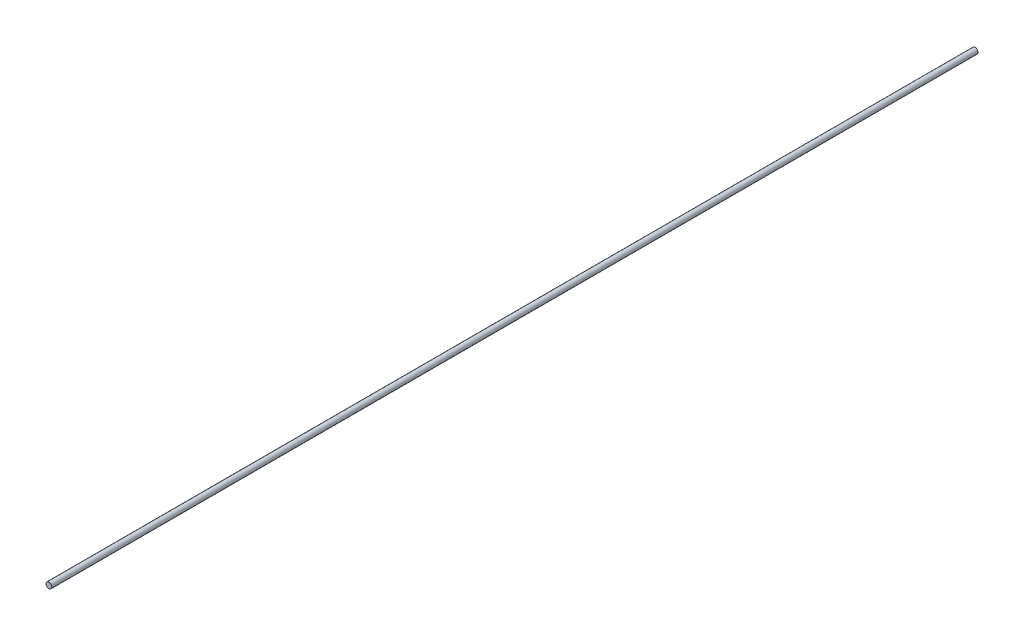
SolidWorks part; units mm, degrees
material "Hexcel AS4C (3000 Filaments)"
ref_plane "Front Plane" through (0, 0, 0) normal (0, 0, 1) x (1, 0, 0)
ref_plane "Top Plane" through (0, 0, 0) normal (0, 1, 0) x (1, 0, 0)
ref_plane "Right Plane" through (0, 0, 0) normal (1, 0, 0) x (0, 0, -1)
sketch "Sketch1" plane through (0, 0, 0) normal (0, 0, 1) x (1, 0, 0)
  circle A1 centre (-70.4276, -2.9481) radius 2.3813
extrude "Boss-Extrude1" add sketch "Sketch1" against normal up to surface (761.9997 mm away)
